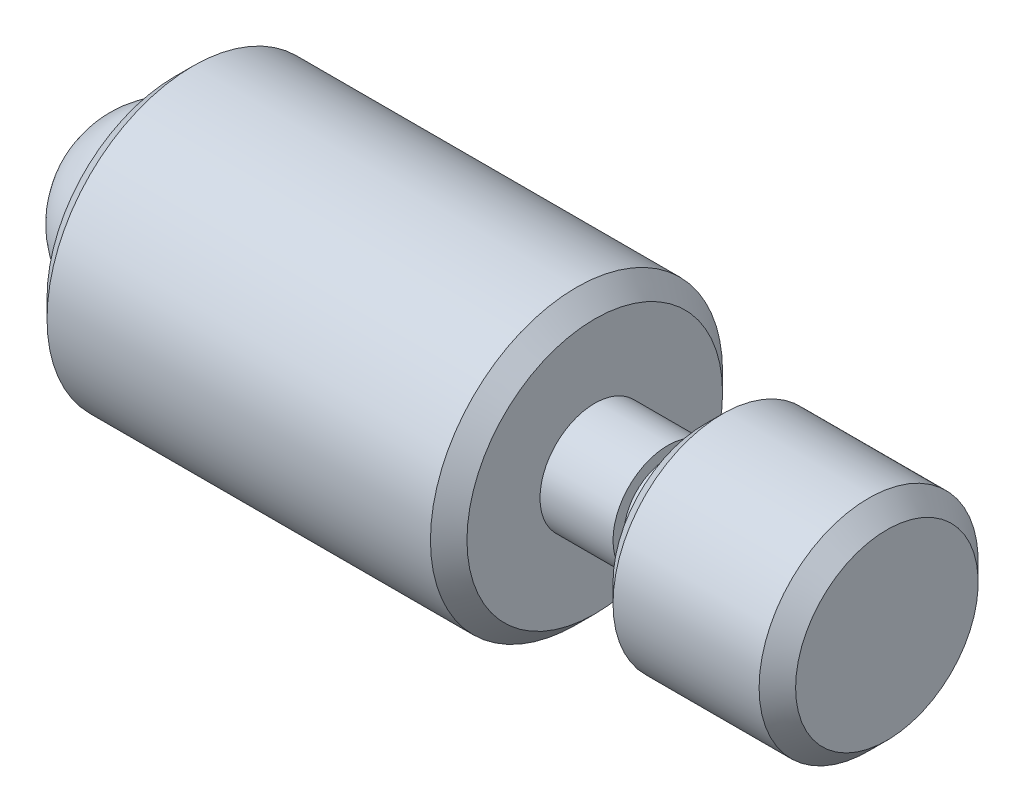
SolidWorks part; units mm, degrees
ref_plane "前视基准面" through (0, 0, 0) normal (0, 0, 1) x (1, 0, 0)
ref_plane "上视基准面" through (0, 0, 0) normal (0, 1, 0) x (1, 0, 0)
ref_plane "右视基准面" through (0, 0, 0) normal (1, 0, 0) x (0, 0, -1)
sketch "草图1" plane through (0, 0, 0) normal (0, 0, 1) x (1, 0, 0)
  line L0 (2.5, 2.5) -> (2.5, 3.5)
  line L1 (2.5, 3.5) -> (3, 4)
  line L2 (3, 4) -> (13.5, 4)
  line L3 (13.5, 4) -> (14, 3.5)
  line L4 (14, 3.5) -> (14, 1.5)
  line L5 (14, 1.5) -> (16, 1.5)
  line L6 (16, 1.5) -> (16, 1.2)
  line L7 (16, 1.2) -> (17, 1.2)
  line L8 (17, 1.2) -> (17, 2.5)
  line L9 (17, 2.5) -> (17.5, 3)
  line L10 (17.5, 3) -> (21.5, 3)
  line L11 (21.5, 3) -> (22, 2.5)
  line L12 (22, 2.5) -> (22, 0)
  line L13 (22, 0) -> (0, 0)
  line L14 (22, 0) -> (0, 0) construction
  arc A0 (0, 0) -> (2.5, 2.5) centre (2.5, 0) cw
revolve "旋转1" add sketch "草图1" angle 360 about L14 reverse direction yes
ref_plane "s_to_b XY" through (0, 0, 0) normal (1, 0, 0) x (0, 0, -1)
ref_plane "s_to_b XZ" through (0, 0, 0) normal (0, -1, 0) x (-1, 0, 0)
ref_plane "s_to_b YZ" through (0, 0, 0) normal (0, 0, -1) x (-1, 0, 0)
ref_axis "s_to_b X" through (0, 0, 80.9) along (0, 0, -1)
ref_axis "s_to_b Y" through (0, -50, 0) along (0, 1, 0)
ref_axis "s_to_b Z" through (80.9, 0, 0) along (-1, 0, 0)
sketch3d "s_to_b"
  point P0 (0, 0, 0)
